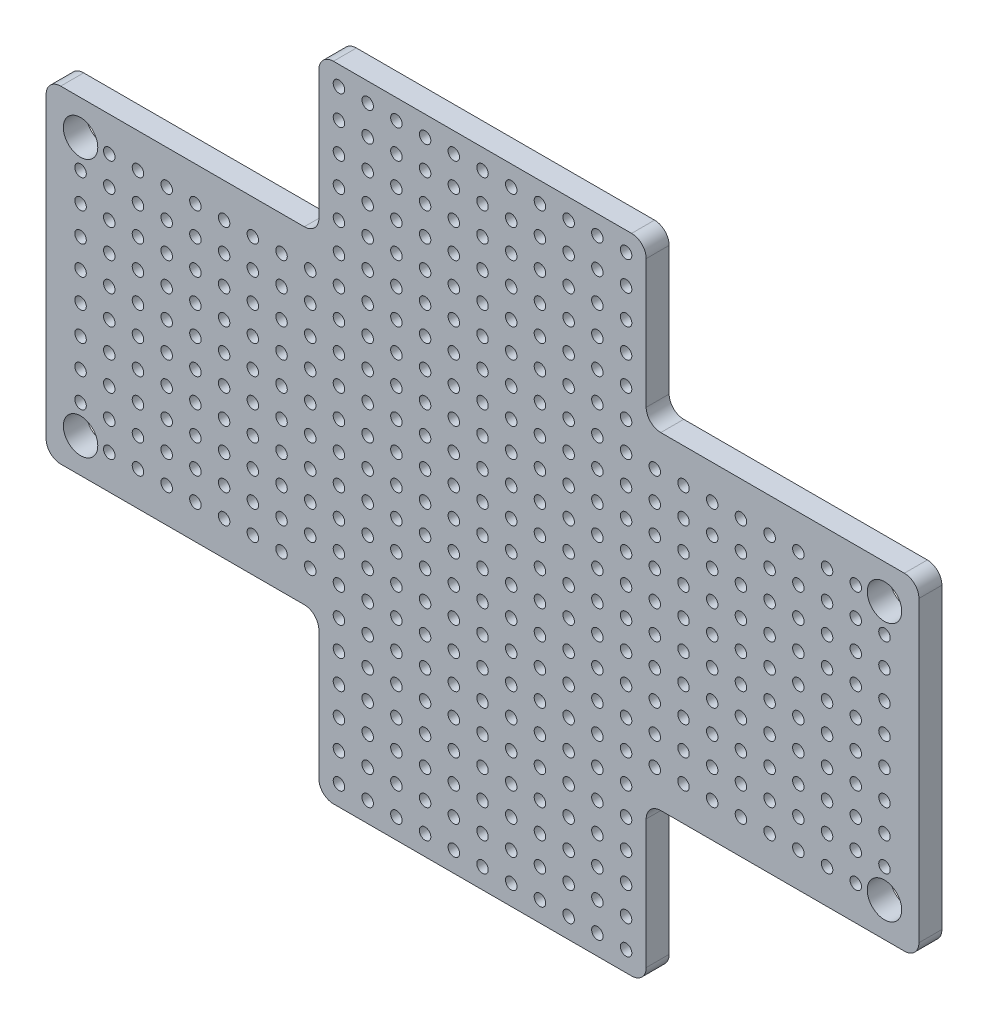
SolidWorks part; units mm, degrees
ref_plane "Front Plane" through (0, 0, 0) normal (0, 0, 1) x (1, 0, 0)
ref_plane "Top Plane" through (0, 0, 0) normal (0, 1, 0) x (1, 0, 0)
ref_plane "Right Plane" through (0, 0, 0) normal (1, 0, 0) x (0, 0, -1)
sketch "Sketch1" plane through (0, 0, 0) normal (0, 0, 1) x (1, 0, 0)
  line L0 (0, 14.25) -> (76, 14.25) construction
  line L1 (0, 0) -> (23.75, 0)
  line L2 (0, 0) -> (0, 28.5)
  line L3 (0, 28.5) -> (23.75, 28.5)
  line L4 (76, 0) -> (76, 28.5)
  line L5 (38, -42.734) -> (38, 127.234) construction
  line L6 (0, 25.5) -> (76, 25.5) construction
  line L7 (76, 3) -> (0, 3) construction
  line L8 (73, 0) -> (73, 28.5) construction
  line L9 (3, 0) -> (3, 28.5) construction
  line L10 (28, 35.5) -> (28, 38.04) construction
  line L12 (23.75, 28.5) -> (23.75, 42.25)
  line L13 (23.75, 42.25) -> (52.25, 42.25)
  line L14 (52.25, 42.25) -> (52.25, 28.5)
  line L15 (52.25, -13.75) -> (52.25, 0)
  line L16 (23.75, -13.75) -> (52.25, -13.75)
  line L17 (23.75, 0) -> (23.75, -13.75)
  line L18 (52.25, 28.5) -> (76, 28.5)
  line L19 (52.25, 0) -> (76, 0)
  line L20 (25.5, 25.5) -> (25.5, 28) construction
  circle A0 centre (3, 25.5) radius 1.5
  circle A1 centre (73, 25.5) radius 1.5
  circle A2 centre (3, 3) radius 1.5
  circle A3 centre (73, 3) radius 1.5
  circle A4 centre (28, 38.04) radius 0.5
  circle A5 centre (5.5, 3) radius 0.5
  circle A6 centre (8, 3) radius 0.5
  circle A7 centre (10.5, 3) radius 0.5
  circle A8 centre (13, 3) radius 0.5
  circle A9 centre (15.5, 3) radius 0.5
  circle A10 centre (18, 3) radius 0.5
  circle A11 centre (20.5, 3) radius 0.5
  circle A12 centre (23, 3) radius 0.5
  circle A13 centre (25.5, 3) radius 0.5
  circle A14 centre (28, 3) radius 0.5
  circle A15 centre (30.5, 3) radius 0.5
  circle A16 centre (33, 3) radius 0.5
  circle A17 centre (35.5, 3) radius 0.5
  circle A18 centre (38, 3) radius 0.5
  circle A19 centre (40.5, 3) radius 0.5
  circle A20 centre (43, 3) radius 0.5
  circle A21 centre (45.5, 3) radius 0.5
  circle A22 centre (48, 3) radius 0.5
  circle A23 centre (50.5, 3) radius 0.5
  circle A24 centre (53, 3) radius 0.5
  circle A25 centre (55.5, 3) radius 0.5
  circle A26 centre (58, 3) radius 0.5
  circle A27 centre (60.5, 3) radius 0.5
  circle A28 centre (63, 3) radius 0.5
  circle A29 centre (65.5, 3) radius 0.5
  circle A30 centre (68, 3) radius 0.5
  circle A31 centre (70.5, 3) radius 0.5
  circle A32 centre (25.5, 38.04) radius 0.5
  circle A33 centre (5.5, 5.5) radius 0.5
  circle A34 centre (8, 5.5) radius 0.5
  circle A35 centre (10.5, 5.5) radius 0.5
  circle A36 centre (13, 5.5) radius 0.5
  circle A37 centre (15.5, 5.5) radius 0.5
  circle A38 centre (18, 5.5) radius 0.5
  circle A39 centre (20.5, 5.5) radius 0.5
  circle A40 centre (23, 5.5) radius 0.5
  circle A41 centre (25.5, 5.5) radius 0.5
  circle A42 centre (28, 5.5) radius 0.5
  circle A43 centre (30.5, 5.5) radius 0.5
  circle A44 centre (33, 5.5) radius 0.5
  circle A45 centre (35.5, 5.5) radius 0.5
  circle A46 centre (38, 5.5) radius 0.5
  circle A47 centre (40.5, 5.5) radius 0.5
  circle A48 centre (43, 5.5) radius 0.5
  circle A49 centre (45.5, 5.5) radius 0.5
  circle A50 centre (48, 5.5) radius 0.5
  circle A51 centre (50.5, 5.5) radius 0.5
  circle A52 centre (53, 5.5) radius 0.5
  circle A53 centre (55.5, 5.5) radius 0.5
  circle A54 centre (58, 5.5) radius 0.5
  circle A55 centre (60.5, 5.5) radius 0.5
  circle A56 centre (63, 5.5) radius 0.5
  circle A57 centre (65.5, 5.5) radius 0.5
  circle A58 centre (68, 5.5) radius 0.5
  circle A59 centre (70.5, 5.5) radius 0.5
  circle A60 centre (73, 5.5) radius 0.5
  circle A61 centre (5.5, 8) radius 0.5
  circle A62 centre (8, 8) radius 0.5
  circle A63 centre (10.5, 8) radius 0.5
  circle A64 centre (13, 8) radius 0.5
  circle A65 centre (15.5, 8) radius 0.5
  circle A66 centre (18, 8) radius 0.5
  circle A67 centre (20.5, 8) radius 0.5
  circle A68 centre (23, 8) radius 0.5
  circle A69 centre (25.5, 8) radius 0.5
  circle A70 centre (28, 8) radius 0.5
  circle A71 centre (30.5, 8) radius 0.5
  circle A72 centre (33, 8) radius 0.5
  circle A73 centre (35.5, 8) radius 0.5
  circle A74 centre (38, 8) radius 0.5
  circle A75 centre (40.5, 8) radius 0.5
  circle A76 centre (43, 8) radius 0.5
  circle A77 centre (45.5, 8) radius 0.5
  circle A78 centre (48, 8) radius 0.5
  circle A79 centre (50.5, 8) radius 0.5
  circle A80 centre (53, 8) radius 0.5
  circle A81 centre (55.5, 8) radius 0.5
  circle A82 centre (58, 8) radius 0.5
  circle A83 centre (60.5, 8) radius 0.5
  circle A84 centre (63, 8) radius 0.5
  circle A85 centre (65.5, 8) radius 0.5
  circle A86 centre (68, 8) radius 0.5
  circle A87 centre (70.5, 8) radius 0.5
  circle A88 centre (73, 8) radius 0.5
  circle A89 centre (5.5, 10.5) radius 0.5
  circle A90 centre (8, 10.5) radius 0.5
  circle A91 centre (10.5, 10.5) radius 0.5
  circle A92 centre (13, 10.5) radius 0.5
  circle A93 centre (15.5, 10.5) radius 0.5
  circle A94 centre (18, 10.5) radius 0.5
  circle A95 centre (20.5, 10.5) radius 0.5
  circle A96 centre (23, 10.5) radius 0.5
  circle A97 centre (25.5, 10.5) radius 0.5
  circle A98 centre (28, 10.5) radius 0.5
  circle A99 centre (30.5, 10.5) radius 0.5
  circle A100 centre (33, 10.5) radius 0.5
  circle A101 centre (35.5, 10.5) radius 0.5
  circle A102 centre (38, 10.5) radius 0.5
  circle A103 centre (40.5, 10.5) radius 0.5
  circle A104 centre (43, 10.5) radius 0.5
  circle A105 centre (45.5, 10.5) radius 0.5
  circle A106 centre (48, 10.5) radius 0.5
  circle A107 centre (50.5, 10.5) radius 0.5
  circle A108 centre (53, 10.5) radius 0.5
  circle A109 centre (55.5, 10.5) radius 0.5
  circle A110 centre (58, 10.5) radius 0.5
  circle A111 centre (60.5, 10.5) radius 0.5
  circle A112 centre (63, 10.5) radius 0.5
  circle A113 centre (65.5, 10.5) radius 0.5
  circle A114 centre (68, 10.5) radius 0.5
  circle A115 centre (70.5, 10.5) radius 0.5
  circle A116 centre (73, 10.5) radius 0.5
  circle A117 centre (5.5, 13) radius 0.5
  circle A118 centre (8, 13) radius 0.5
  circle A119 centre (10.5, 13) radius 0.5
  circle A120 centre (13, 13) radius 0.5
  circle A121 centre (15.5, 13) radius 0.5
  circle A122 centre (18, 13) radius 0.5
  circle A123 centre (20.5, 13) radius 0.5
  circle A124 centre (23, 13) radius 0.5
  circle A125 centre (25.5, 13) radius 0.5
  circle A126 centre (28, 13) radius 0.5
  circle A127 centre (30.5, 13) radius 0.5
  circle A128 centre (33, 13) radius 0.5
  circle A129 centre (35.5, 13) radius 0.5
  circle A130 centre (38, 13) radius 0.5
  circle A131 centre (40.5, 13) radius 0.5
  circle A132 centre (43, 13) radius 0.5
  circle A133 centre (45.5, 13) radius 0.5
  circle A134 centre (48, 13) radius 0.5
  circle A135 centre (50.5, 13) radius 0.5
  circle A136 centre (53, 13) radius 0.5
  circle A137 centre (55.5, 13) radius 0.5
  circle A138 centre (58, 13) radius 0.5
  circle A139 centre (60.5, 13) radius 0.5
  circle A140 centre (63, 13) radius 0.5
  circle A141 centre (65.5, 13) radius 0.5
  circle A142 centre (68, 13) radius 0.5
  circle A143 centre (70.5, 13) radius 0.5
  circle A144 centre (73, 13) radius 0.5
  circle A145 centre (5.5, 15.5) radius 0.5
  circle A146 centre (8, 15.5) radius 0.5
  circle A147 centre (10.5, 15.5) radius 0.5
  circle A148 centre (13, 15.5) radius 0.5
  circle A149 centre (15.5, 15.5) radius 0.5
  circle A150 centre (18, 15.5) radius 0.5
  circle A151 centre (20.5, 15.5) radius 0.5
  circle A152 centre (23, 15.5) radius 0.5
  circle A153 centre (25.5, 15.5) radius 0.5
  circle A154 centre (28, 15.5) radius 0.5
  circle A155 centre (30.5, 15.5) radius 0.5
  circle A156 centre (33, 15.5) radius 0.5
  circle A157 centre (35.5, 15.5) radius 0.5
  circle A158 centre (38, 15.5) radius 0.5
  circle A159 centre (40.5, 15.5) radius 0.5
  circle A160 centre (43, 15.5) radius 0.5
  circle A161 centre (45.5, 15.5) radius 0.5
  circle A162 centre (48, 15.5) radius 0.5
  circle A163 centre (50.5, 15.5) radius 0.5
  circle A164 centre (53, 15.5) radius 0.5
  circle A165 centre (55.5, 15.5) radius 0.5
  circle A166 centre (58, 15.5) radius 0.5
  circle A167 centre (60.5, 15.5) radius 0.5
  circle A168 centre (63, 15.5) radius 0.5
  circle A169 centre (65.5, 15.5) radius 0.5
  circle A170 centre (68, 15.5) radius 0.5
  circle A171 centre (70.5, 15.5) radius 0.5
  circle A172 centre (73, 15.5) radius 0.5
  circle A173 centre (5.5, 18) radius 0.5
  circle A174 centre (8, 18) radius 0.5
  circle A175 centre (10.5, 18) radius 0.5
  circle A176 centre (13, 18) radius 0.5
  circle A177 centre (15.5, 18) radius 0.5
  circle A178 centre (18, 18) radius 0.5
  circle A179 centre (20.5, 18) radius 0.5
  circle A180 centre (23, 18) radius 0.5
  circle A181 centre (25.5, 18) radius 0.5
  circle A182 centre (28, 18) radius 0.5
  circle A183 centre (30.5, 18) radius 0.5
  circle A184 centre (33, 18) radius 0.5
  circle A185 centre (35.5, 18) radius 0.5
  circle A186 centre (38, 18) radius 0.5
  circle A187 centre (40.5, 18) radius 0.5
  circle A188 centre (43, 18) radius 0.5
  circle A189 centre (45.5, 18) radius 0.5
  circle A190 centre (48, 18) radius 0.5
  circle A191 centre (50.5, 18) radius 0.5
  circle A192 centre (53, 18) radius 0.5
  circle A193 centre (55.5, 18) radius 0.5
  circle A194 centre (58, 18) radius 0.5
  circle A195 centre (60.5, 18) radius 0.5
  circle A196 centre (63, 18) radius 0.5
  circle A197 centre (65.5, 18) radius 0.5
  circle A198 centre (68, 18) radius 0.5
  circle A199 centre (70.5, 18) radius 0.5
  circle A200 centre (73, 18) radius 0.5
  circle A201 centre (5.5, 20.5) radius 0.5
  circle A202 centre (8, 20.5) radius 0.5
  circle A203 centre (10.5, 20.5) radius 0.5
  circle A204 centre (13, 20.5) radius 0.5
  circle A205 centre (15.5, 20.5) radius 0.5
  circle A206 centre (18, 20.5) radius 0.5
  circle A207 centre (20.5, 20.5) radius 0.5
  circle A208 centre (23, 20.5) radius 0.5
  circle A209 centre (25.5, 20.5) radius 0.5
  circle A210 centre (28, 20.5) radius 0.5
  circle A211 centre (30.5, 20.5) radius 0.5
  circle A212 centre (33, 20.5) radius 0.5
  circle A213 centre (35.5, 20.5) radius 0.5
  circle A214 centre (38, 20.5) radius 0.5
  circle A215 centre (40.5, 20.5) radius 0.5
  circle A216 centre (43, 20.5) radius 0.5
  circle A217 centre (45.5, 20.5) radius 0.5
  circle A218 centre (48, 20.5) radius 0.5
  circle A219 centre (50.5, 20.5) radius 0.5
  circle A220 centre (53, 20.5) radius 0.5
  circle A221 centre (55.5, 20.5) radius 0.5
  circle A222 centre (58, 20.5) radius 0.5
  circle A223 centre (60.5, 20.5) radius 0.5
  circle A224 centre (63, 20.5) radius 0.5
  circle A225 centre (65.5, 20.5) radius 0.5
  circle A226 centre (68, 20.5) radius 0.5
  circle A227 centre (70.5, 20.5) radius 0.5
  circle A228 centre (73, 20.5) radius 0.5
  circle A229 centre (5.5, 23) radius 0.5
  circle A230 centre (8, 23) radius 0.5
  circle A231 centre (10.5, 23) radius 0.5
  circle A232 centre (13, 23) radius 0.5
  circle A233 centre (15.5, 23) radius 0.5
  circle A234 centre (18, 23) radius 0.5
  circle A235 centre (20.5, 23) radius 0.5
  circle A236 centre (23, 23) radius 0.5
  circle A237 centre (25.5, 23) radius 0.5
  circle A238 centre (28, 23) radius 0.5
  circle A239 centre (30.5, 23) radius 0.5
  circle A240 centre (33, 23) radius 0.5
  circle A241 centre (35.5, 23) radius 0.5
  circle A242 centre (38, 23) radius 0.5
  circle A243 centre (40.5, 23) radius 0.5
  circle A244 centre (43, 23) radius 0.5
  circle A245 centre (45.5, 23) radius 0.5
  circle A246 centre (48, 23) radius 0.5
  circle A247 centre (50.5, 23) radius 0.5
  circle A248 centre (53, 23) radius 0.5
  circle A249 centre (55.5, 23) radius 0.5
  circle A250 centre (58, 23) radius 0.5
  circle A251 centre (60.5, 23) radius 0.5
  circle A252 centre (63, 23) radius 0.5
  circle A253 centre (65.5, 23) radius 0.5
  circle A254 centre (68, 23) radius 0.5
  circle A255 centre (70.5, 23) radius 0.5
  circle A256 centre (73, 23) radius 0.5
  circle A257 centre (5.5, 25.5) radius 0.5
  circle A258 centre (8, 25.5) radius 0.5
  circle A259 centre (10.5, 25.5) radius 0.5
  circle A260 centre (13, 25.5) radius 0.5
  circle A261 centre (15.5, 25.5) radius 0.5
  circle A262 centre (18, 25.5) radius 0.5
  circle A263 centre (20.5, 25.5) radius 0.5
  circle A264 centre (23, 25.5) radius 0.5
  circle A265 centre (25.5, 25.5) radius 0.5
  circle A266 centre (28, 25.5) radius 0.5
  circle A267 centre (30.5, 25.5) radius 0.5
  circle A268 centre (33, 25.5) radius 0.5
  circle A269 centre (35.5, 25.5) radius 0.5
  circle A270 centre (38, 25.5) radius 0.5
  circle A271 centre (40.5, 25.5) radius 0.5
  circle A272 centre (43, 25.5) radius 0.5
  circle A273 centre (45.5, 25.5) radius 0.5
  circle A274 centre (48, 25.5) radius 0.5
  circle A275 centre (50.5, 25.5) radius 0.5
  circle A276 centre (53, 25.5) radius 0.5
  circle A277 centre (55.5, 25.5) radius 0.5
  circle A278 centre (58, 25.5) radius 0.5
  circle A279 centre (60.5, 25.5) radius 0.5
  circle A280 centre (63, 25.5) radius 0.5
  circle A281 centre (65.5, 25.5) radius 0.5
  circle A282 centre (68, 25.5) radius 0.5
  circle A283 centre (70.5, 25.5) radius 0.5
  circle A284 centre (28, 40.58) radius 0.5
  circle A285 centre (3, 5.5) radius 0.5
  circle A286 centre (3, 8) radius 0.5
  circle A287 centre (3, 10.5) radius 0.5
  circle A288 centre (3, 13) radius 0.5
  circle A289 centre (3, 15.5) radius 0.5
  circle A290 centre (3, 18) radius 0.5
  circle A291 centre (3, 20.5) radius 0.5
  circle A292 centre (3, 23) radius 0.5
  circle A293 centre (25.5, 40.58) radius 0.5
  circle A294 centre (25.5, 28) radius 0.5
  circle A295 centre (28, 28) radius 0.5
  circle A296 centre (30.5, 28) radius 0.5
  circle A297 centre (33, 28) radius 0.5
  circle A298 centre (35.5, 28) radius 0.5
  circle A299 centre (38, 28) radius 0.5
  circle A300 centre (40.5, 28) radius 0.5
  circle A301 centre (43, 28) radius 0.5
  circle A302 centre (45.5, 28) radius 0.5
  circle A303 centre (48, 28) radius 0.5
  circle A304 centre (50.5, 28) radius 0.5
  circle A305 centre (25.5, 30.5) radius 0.5
  circle A306 centre (28, 30.5) radius 0.5
  circle A307 centre (30.5, 30.5) radius 0.5
  circle A308 centre (33, 30.5) radius 0.5
  circle A309 centre (35.5, 30.5) radius 0.5
  circle A310 centre (38, 30.5) radius 0.5
  circle A311 centre (40.5, 30.5) radius 0.5
  circle A312 centre (43, 30.5) radius 0.5
  circle A313 centre (45.5, 30.5) radius 0.5
  circle A314 centre (48, 30.5) radius 0.5
  circle A315 centre (50.5, 30.5) radius 0.5
  circle A316 centre (25.5, 33) radius 0.5
  circle A317 centre (28, 33) radius 0.5
  circle A318 centre (30.5, 33) radius 0.5
  circle A319 centre (33, 33) radius 0.5
  circle A320 centre (35.5, 33) radius 0.5
  circle A321 centre (38, 33) radius 0.5
  circle A322 centre (40.5, 33) radius 0.5
  circle A323 centre (43, 33) radius 0.5
  circle A324 centre (45.5, 33) radius 0.5
  circle A325 centre (48, 33) radius 0.5
  circle A326 centre (50.5, 33) radius 0.5
  circle A327 centre (25.5, 35.5) radius 0.5
  circle A328 centre (28, 35.5) radius 0.5
  circle A329 centre (30.5, 35.5) radius 0.5
  circle A330 centre (33, 35.5) radius 0.5
  circle A331 centre (35.5, 35.5) radius 0.5
  circle A332 centre (38, 35.5) radius 0.5
  circle A333 centre (40.5, 35.5) radius 0.5
  circle A334 centre (43, 35.5) radius 0.5
  circle A335 centre (45.5, 35.5) radius 0.5
  circle A336 centre (48, 35.5) radius 0.5
  circle A337 centre (50.5, 35.5) radius 0.5
  circle A338 centre (50.5, 38.04) radius 0.5
  circle A339 centre (48, 38.04) radius 0.5
  circle A340 centre (30.5, 38) radius 0.5
  circle A341 centre (33, 38) radius 0.5
  circle A342 centre (35.5, 38) radius 0.5
  circle A343 centre (38, 38) radius 0.5
  circle A344 centre (40.5, 38) radius 0.5
  circle A345 centre (43, 38) radius 0.5
  circle A346 centre (45.5, 38) radius 0.5
  circle A347 centre (50.5, 40.58) radius 0.5
  circle A348 centre (48, 40.58) radius 0.5
  circle A351 centre (30.5, 40.5) radius 0.5
  circle A352 centre (33, 40.5) radius 0.5
  circle A353 centre (35.5, 40.5) radius 0.5
  circle A354 centre (38, 40.5) radius 0.5
  circle A355 centre (40.5, 40.5) radius 0.5
  circle A356 centre (43, 40.5) radius 0.5
  circle A357 centre (45.5, 40.5) radius 0.5
  circle A384 centre (25.5, -12) radius 0.5
  circle A385 centre (25.5, -9.5) radius 0.5
  circle A386 centre (25.5, -7) radius 0.5
  circle A387 centre (25.5, -4.5) radius 0.5
  circle A388 centre (25.5, -2) radius 0.5
  circle A389 centre (25.5, 0.5) radius 0.5
  circle A410 centre (50.5, -12) radius 0.5
  circle A411 centre (48, -12) radius 0.5
  circle A412 centre (45.5, -12) radius 0.5
  circle A413 centre (43, -12) radius 0.5
  circle A414 centre (40.5, -12) radius 0.5
  circle A415 centre (38, -12) radius 0.5
  circle A416 centre (35.5, -12) radius 0.5
  circle A417 centre (33, -12) radius 0.5
  circle A418 centre (30.5, -12) radius 0.5
  circle A419 centre (28, -12) radius 0.5
  circle A420 centre (50.5, -9.5) radius 0.5
  circle A421 centre (48, -9.5) radius 0.5
  circle A422 centre (45.5, -9.5) radius 0.5
  circle A423 centre (43, -9.5) radius 0.5
  circle A424 centre (40.5, -9.5) radius 0.5
  circle A425 centre (38, -9.5) radius 0.5
  circle A426 centre (35.5, -9.5) radius 0.5
  circle A427 centre (33, -9.5) radius 0.5
  circle A428 centre (30.5, -9.5) radius 0.5
  circle A429 centre (28, -9.5) radius 0.5
  circle A430 centre (50.5, -7) radius 0.5
  circle A431 centre (48, -7) radius 0.5
  circle A432 centre (45.5, -7) radius 0.5
  circle A433 centre (43, -7) radius 0.5
  circle A434 centre (40.5, -7) radius 0.5
  circle A435 centre (38, -7) radius 0.5
  circle A436 centre (35.5, -7) radius 0.5
  circle A437 centre (33, -7) radius 0.5
  circle A438 centre (30.5, -7) radius 0.5
  circle A439 centre (28, -7) radius 0.5
  circle A440 centre (50.5, -4.5) radius 0.5
  circle A441 centre (48, -4.5) radius 0.5
  circle A442 centre (45.5, -4.5) radius 0.5
  circle A443 centre (43, -4.5) radius 0.5
  circle A444 centre (40.5, -4.5) radius 0.5
  circle A445 centre (38, -4.5) radius 0.5
  circle A446 centre (35.5, -4.5) radius 0.5
  circle A447 centre (33, -4.5) radius 0.5
  circle A448 centre (30.5, -4.5) radius 0.5
  circle A449 centre (28, -4.5) radius 0.5
  circle A450 centre (50.5, -2) radius 0.5
  circle A451 centre (48, -2) radius 0.5
  circle A452 centre (45.5, -2) radius 0.5
  circle A453 centre (43, -2) radius 0.5
  circle A454 centre (40.5, -2) radius 0.5
  circle A455 centre (38, -2) radius 0.5
  circle A456 centre (35.5, -2) radius 0.5
  circle A457 centre (33, -2) radius 0.5
  circle A458 centre (30.5, -2) radius 0.5
  circle A459 centre (28, -2) radius 0.5
  circle A460 centre (50.5, 0.5) radius 0.5
  circle A461 centre (48, 0.5) radius 0.5
  circle A462 centre (45.5, 0.5) radius 0.5
  circle A463 centre (43, 0.5) radius 0.5
  circle A464 centre (40.5, 0.5) radius 0.5
  circle A465 centre (38, 0.5) radius 0.5
  circle A466 centre (35.5, 0.5) radius 0.5
  circle A467 centre (33, 0.5) radius 0.5
  circle A468 centre (30.5, 0.5) radius 0.5
  circle A469 centre (28, 0.5) radius 0.5
  circle A571 centre (3, 3) radius 1.5 [skipped]
  circle A572 centre (25.5, 40.5) radius 0.5 [skipped]
  circle A573 centre (50.5, 40.5) radius 0.5 [skipped]
  circle A574 centre (25.5, 38) radius 0.5 [skipped]
  circle A575 centre (28, 38) radius 0.5 [skipped]
  circle A576 centre (28, 40.5) radius 0.5 [skipped]
  circle A577 centre (48, 40.5) radius 0.5 [skipped]
  circle A578 centre (48, 38) radius 0.5 [skipped]
  circle A579 centre (50.5, 38) radius 0.5 [skipped]
  point P611 (38, 42.25)
  point P612 (38, 14.25)
  dimension "D3" = 3
  dimension "D8" = 3
  dimension "D9" = 11.25
  dimension "D10" = 76
  dimension "D11" = 35
  dimension "D12" = 3
  dimension "D13" = 2.54
  dimension "D14" = 3
  dimension "D15" = 1
  dimension "D20" = 2.5
  dimension "D1" = 28.5
  dimension "D2" = 3
  dimension "D4" = 3
  dimension "D5" = 3
  dimension "D16" = 28.5
  dimension "D17" = 13.75
  dimension "D19" = 2.5
  dimension "D6" = 2
  dimension "D7" = 2
  dimension "D18" = 7
extrude "Boss-Extrude1" add sketch "Sketch1" along normal blind 2
fillet "Fillet1" [suppressed] radius 1.27
ref_plane "Plane1" [suppressed] through (0, 14.25, 0) normal (0, -1, 0) x (1, 0, 0)
ref_plane "Plane2" [suppressed] through (38, 0, 0) normal (1, 0, 0) x (0, 0, -1)
fillet "Fillet2" radius 1.27 12 edges at (0, 0, 1) (23.75, 0, 1) (23.75, -13.75, 1) (52.25, -13.75, 1) (52.25, 0, 1) (76, 0, 1) (76, 28.5, 1) (52.25, 28.5, 1) (52.25, 42.25, 1) (23.75, 42.25, 1) (23.75, 28.5, 1) (0, 28.5, 1)
